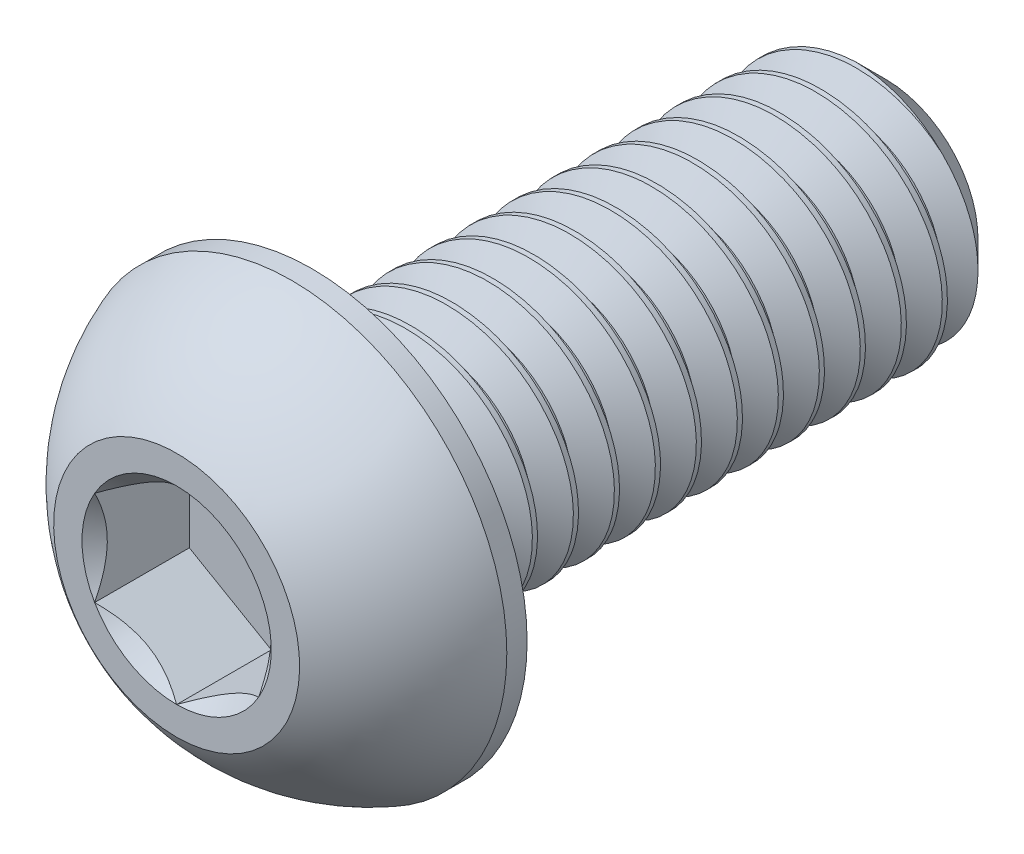
SolidWorks part; units mm, degrees
note: '?' marks a value the reader was unsure of.
ref_plane "Front" through (0, 0, 0) normal (0, 0, 1) x (1, 0, 0)
ref_plane "Top" through (0, 0, 0) normal (0, 1, 0) x (1, 0, 0)
ref_plane "Right" through (0, 0, 0) normal (1, 0, 0) x (0, 0, -1)
sketch "Sketch1" plane through (0, 0, 0) normal (1, 0, 0) x (0, 0, -1)
  line L2 (3.3, 3) -> (17.3, 3)
  line L3 (17.3, 3) -> (17.3, 0)
  line L4 (17.3, 0) -> (3.3, 0)
  line L6 (2.805, 5.25) -> (3.3, 5.25) construction
  line L7 (17.3, 3) -> (17.3, -3) construction
  line L8 (0, 0) -> (3.3, 0) construction
  line L9 (3.3, 5.25) -> (3.3, -5.25) construction
  line L11 (3.3, 3) -> (3.3, 0)
  line L13 (0, 2) -> (0, -2) construction
  line L14 (0, 2) -> (0, 3) construction
  arc A3 (0, 3) -> (2.805, 5.25) centre (4.7113, 0) cw construction
  dimension "D1" = 0.495
revolve "Revolve1" add sketch "Sketch1" angle 360 mid plane about L4
sketch "Sketch3" plane through (0, 0, -17.3) normal (0, 0, -1) x (-1, 0, 0)
  circle A0 centre (0, 0) radius 3
curve "Helix/Spiral1" pitch 1 height 15 turns 15
chamfer "Chamfer1" distance 0.75 angle 45 1 edges at (0, 3, -17.3)
sketch "Sketch7" plane through (0, 0, 0) normal (1, 0, 0) x (0, 0, -1)
  line L6 (2.805, 5.25) -> (3.3, 5.25) construction
  line L8 (0, 0) -> (3.3, 0) construction
  line L11 (3.3, 5.25) -> (3.3, -5.25) construction
  line L12 (2.805, 5.25) -> (3.3, 5.25)
  line L13 (0, 0) -> (3.3, 0)
  line L14 (0, 2) -> (0, -2) construction
  line L15 (3.3, 5.25) -> (3.3, 0)
  line L16 (0, 3) -> (0, 0)
  arc A2 (2.805, 5.25) -> (0, 3) centre (4.7113, 0) ccw construction
  arc A3 (2.805, 5.25) -> (0, 3) centre (4.7113, 0) ccw
revolve "Revolve2" add sketch "Sketch7" angle 360 mid plane about L13
sketch "Sketch5" plane through (0, 0, 0) normal (0, 0, 1) x (1, 0, 0)
  line L1 (2, -1.1547) -> (2, 1.1547)
  line L2 (2, 1.1547) -> (0, 2.3094)
  line L3 (0, 2.3094) -> (-2, 1.1547)
  line L4 (-2, 1.1547) -> (-2, -1.1547)
  line L5 (-2, -1.1547) -> (0, -2.3094)
  line L6 (0, -2.3094) -> (2, -1.1547)
  circle A0 centre (0, 0) radius 2 construction
extrude "Cut-Extrude2" cut sketch "Sketch5" against normal blind 2.31
sketch "Sketch6" plane through (0, 0, 0) normal (0, 0, 1) x (1, 0, 0)
  circle A0 centre (0, 0) radius 2.3094
extrude "Cut-Extrude3" cut sketch "Sketch6" against normal blind 2.31 draft 45
sketch "Sketch2" plane through (0, 0, 0) normal (1, 0, 0) x (0, 0, -1)
  line L0 (16.55, 3) -> (17.425, 3)
  line L1 (17.425, 3) -> (17.05, 2.3505)
  line L2 (17.05, 2.3505) -> (16.925, 2.3505)
  line L3 (16.925, 2.3505) -> (16.55, 3)
  line L4 (16.7375, 2.6752) -> (17.2375, 2.6752) construction
  dimension "D1" = 60
  dimension "D2" = 0.125
  dimension "D3" = 0.5
sweep "Cut-Sweep1" cut profiles "Sketch2" path "Helix/Spiral1"
sketch "Sketch10" plane through (0, 0, 0) normal (1, 0, 0) x (0, 0, -1)
  line L0 (17.3, 3) -> (17.3, -3) construction
  point P0 (15.8, -3)
  dimension "D1" = 1.5
ref_axis "Center Axis 1" through (0, 0, -8.1113) along (0, 0, 1)?
ref_plane "Contact Plane 1" through (0, 0, -3.3) normal (0, 0, -1) x (-1, 0, 0)
ref_plane "Contact Plane 2" through (0, 0, 0) normal (0, 0, 1) x (1, 0, 0)
equation "\"D3@Helix/Spiral1\" = \"Lg@Sketch1\" + \"D4@Helix/Spiral1\""
equation "\"D2@Sketch2\" = \"D4@Helix/Spiral1\" * .125"
equation "\"D3@Sketch2\" = \"D4@Helix/Spiral1\" * .5"
equation "\"D1@Chamfer1\" = \"D4@Helix/Spiral1\" * .75"
equation "\"D1@Cut-Extrude2\" = \"Head Ht@Sketch1\" * .7"
equation "\"D1@Sketch1\" = \"Head Ht@Sketch1\" * .15"
equation "\"D1@Sketch10\" = \"D4@Helix/Spiral1\" * 1.5"
equation "\"D1@Cut-Extrude3\" = \"D1@Cut-Extrude2\""
